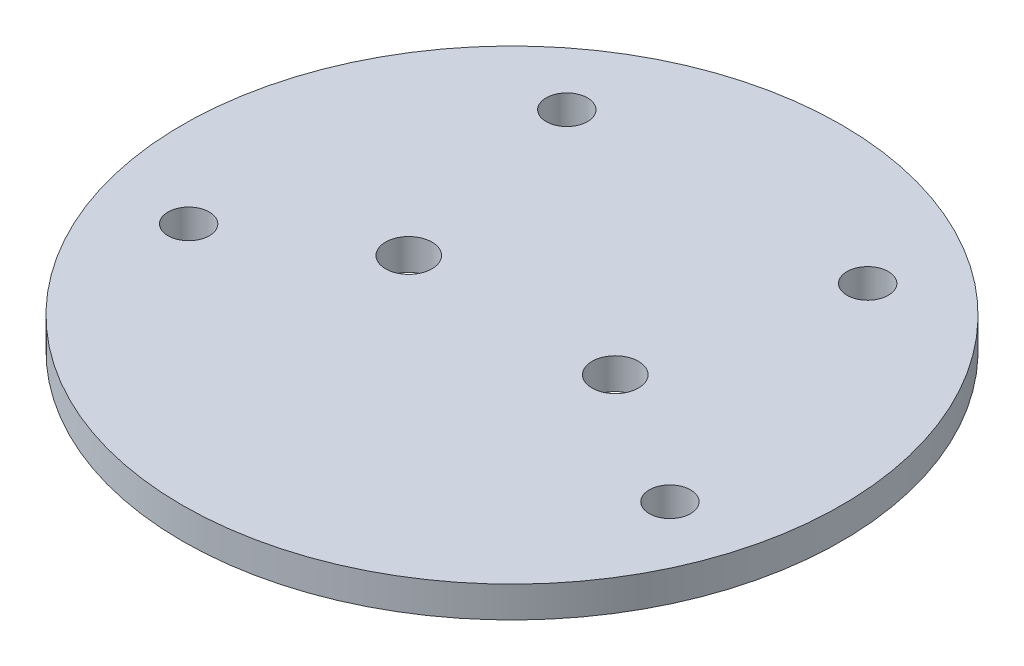
SolidWorks part; units mm, degrees
material "5052-H32"
ref_plane "Front Plane" through (0, 0, 0) normal (0, 0, 1) x (1, 0, 0)
ref_plane "Top Plane" through (0, 0, 0) normal (0, 1, 0) x (1, 0, 0)
ref_plane "Right Plane" through (0, 0, 0) normal (1, 0, 0) x (0, 0, -1)
sketch "Sketch1" plane through (0, 0, 0) normal (0, 1, 0) x (1, 0, 0)
  line L0 (0, 0) -> (-23.1297, 31.5565) construction
  line L1 (0, 0) -> (-41.7254, 0) construction
  line L2 (-37.0005, -12.7186) -> (0, 0) construction
  line L3 (0, -31.6103) -> (0, 47.1695) construction
  circle A0 centre (0, 0) radius 50.673
  circle A3 centre (-15.875, 0) radius 3.5687
  circle A4 centre (15.875, 0) radius 3.5687
  circle A5 centre (-37.0005, -12.7186) radius 3.175
  circle A8 centre (-23.1297, 31.5565) radius 3.175
  circle A9 centre (23.1297, 31.5565) radius 3.175
  circle A10 centre (37.0005, -12.7186) radius 3.175
  dimension "D1" = 101.346
  dimension "D2" = 6.35
  dimension "D3" = 6.35
  dimension "D5" = 15.875
  dimension "D6" = 15.875
  dimension "D4" = 39.1254
  dimension "D7" = 53.76
  dimension "D8" = 39.1254
  dimension "D9" = 18.97
extrude "Boss-Extrude1" add sketch "Sketch1" along normal blind 4.7752
equation "\"allrockets_tube_ID\"= 3.85in"
equation "\"allrockets_tube_OD\"= 4.024in"
equation "\"hole\"= 6.35mm"
equation "\"back_plate_width\"= 28mm"
equation "\"card_spacing\"= 23mm"
equation "\"card_number\"= 6"
equation "\"ToDi\"= 0.05mm"
equation "\"card_diameter\"= 85.86mm"
equation "\"overlap\"= 6.6mm"
equation "\"card_length\"= 68mm"
equation "\"rack_hole_tol\"= 0.35mm"
equation "\"rack_front_width\"= 11.63mm"
equation "\"hole_b_d\"= 39.12541885mm"
equation "\"hole_b_a\"= 18.9721389deg"
equation "\"hole_u_d\"= 39.12541885mm"
equation "\"hole_u_a\"= 53.76090642deg"
equation "\"card_h\"= 61.73mm"
equation "\"sphinx_av\"= 50.292mm"
equation "\"tb_spacing\"= 40mm"
equation "\"D2@Sketch1\"=\"hole\""
equation "\"D4@Sketch1\"=\"hole_u_d\""
equation "\"D7@Sketch1\"=\"hole_u_a\""
equation "\"D8@Sketch1\"=\"hole_b_d\""
equation "\"D9@Sketch1\"=\"hole_b_a\""
